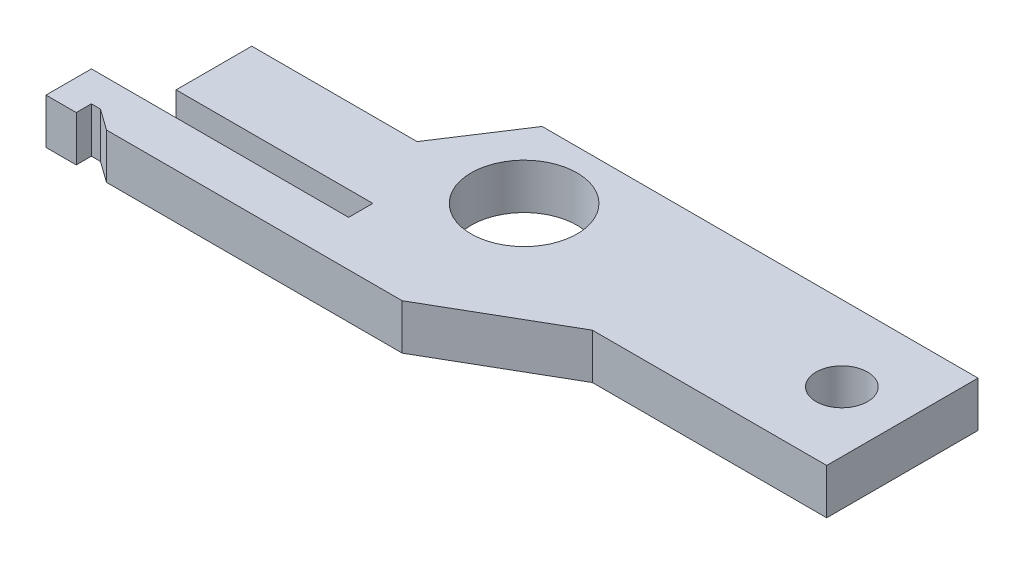
SolidWorks part; units mm, degrees
ref_plane "前视基准面" through (0, 0, 0) normal (0, 0, 1) x (1, 0, 0)
ref_plane "上视基准面" through (0, 0, 0) normal (0, 1, 0) x (1, 0, 0)
ref_plane "右视基准面" through (0, 0, 0) normal (1, 0, 0) x (0, 0, -1)
sketch "草图2" plane through (0, 7.0968, 0) normal (0, 1, 0) x (1, 0, 0)
  line L0 (-1.9, 0) -> (-10.4, 0)
  line L1 (-6.9, 0.7) -> (-6.9, 0) construction
  line L2 (-1.9, 0) -> (-1.9, 0.8)
  line L3 (-1.9, 0.8) -> (-8.4, 0.8)
  line L4 (-6.9, 0.7) -> (-1.9, 0.7) construction
  line L5 (-10.4, 0) -> (-10.4, -1.5)
  line L6 (-10.4, -1.5) -> (-9.4, -1.5)
  line L7 (13.1, 0.8) -> (13.1, 5.8)
  line L8 (-9.4, -1) -> (-9.1, -1)
  line L9 (-9.1, -1) -> (-8.4, -1.5)
  line L10 (-1.3034, 5.8) -> (-2.9368, 3.3)
  line L11 (13.1, 5.8) -> (-1.3034, 5.8)
  line L12 (-8.4, 3.3) -> (-8.4, 0.8)
  line L13 (-9.4, -1.5) -> (-9.4, -1)
  line L15 (1.3718, -1.5) -> (5.3555, 0.8)
  line L16 (5.3555, 0.8) -> (13.1, 0.8)
  line L17 (-8.4, -1.5) -> (1.3718, -1.5)
  line L18 (-2.9368, 3.3) -> (-8.4, 3.3)
  circle A0 centre (11.1, 3.3) radius 0.85
  circle A1 centre (0.6, 3.3) radius 1.75
  point P12 (-4.2542, 3.3)
  point P24 (-1.8036, 5.8)
  point P28 (-2.2144, 3.3)
  dimension "D4" = 1.7
  dimension "D5" = 3.5
  dimension "D1" = 0.1
  dimension "D2" = 1.5
  dimension "D6" = 10.5
  dimension "D7" = 1
  dimension "D8" = 2.5
  dimension "D9" = 0.5
  dimension "D10" = 10
  dimension "D11" = 1.5
  dimension "D12" = 1
  dimension "D13" = 2
  dimension "D14" = 30
  dimension "D15" = 2.5
  dimension "D3" = 5
  dimension "D16" = 0.3
extrude "凸台-拉伸1" add sketch "草图2" against normal blind 1.5
equation "\"D8@草图2\"=\"D3@草图2\"/2"
